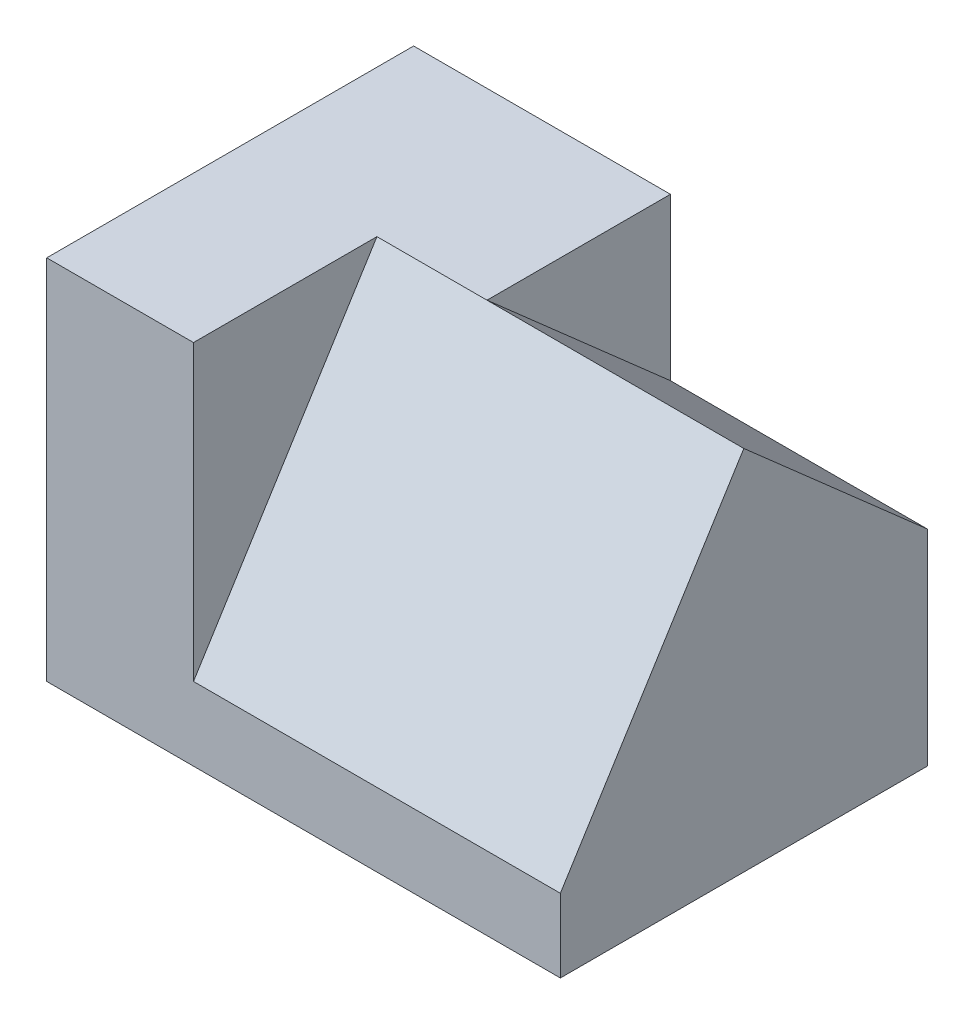
SolidWorks part; units mm, degrees
ref_plane "Front Plane" through (0, 0, 0) normal (0, 0, 1) x (1, 0, 0)
ref_plane "Top Plane" through (0, 0, 0) normal (0, 1, 0) x (1, 0, 0)
ref_plane "Right Plane" through (0, 0, 0) normal (1, 0, 0) x (0, 0, -1)
sketch "Sketch1" plane through (0, 0, 0) normal (0, 1, 0) x (1, 0, 0)
  line L1 (0, 0) -> (1778, 0)
  line L2 (0, 0) -> (0, 1270)
  line L3 (0, 1270) -> (1778, 1270)
  line L4 (1778, 0) -> (1778, 1270)
  dimension "D1" = 1778
  dimension "D2" = 1270
extrude "Boss-Extrude1" add sketch "Sketch1" along normal blind 1270
sketch "Sketch2" plane through (1778, 0, 0) normal (1, 0, 0) x (0, 0, -1)
  line L0 (635, 1270) -> (0, 254)
  line L1 (0, 1270) -> (1270, 1270) construction
  line L2 (0, 1270) -> (0, 0) construction
  line L3 (635, 1270) -> (1270, 711.2)
  line L4 (1270, 1270) -> (1270, 0) construction
  line L5 (0, 0) -> (1270, 0) construction
  line M4 (1270, 0) -> (1270, 1270)
  line M5 (1270, 1270) -> (0, 1270)
  line M6 (0, 1270) -> (0, 0)
  dimension "D1" = 254
  dimension "D2" = 711.2
extrude "Cut-Extrude1" cut sketch "Sketch2" against normal blind 1270 and the other way through all contours L0 M5 M6 region at (1778, 931.3333, -211.6667)
extrude "Cut-Extrude2" cut sketch "Sketch2<4>" against normal blind 889 and the other way through all contours L3 M5 M4 region at (1778, 1083.7333, -1058.3333)
sketch "Sketch2<4>" plane through (1778, 0, 0) normal (1, 0, 0) x (0, 0, -1) same geometry as "Sketch2"
